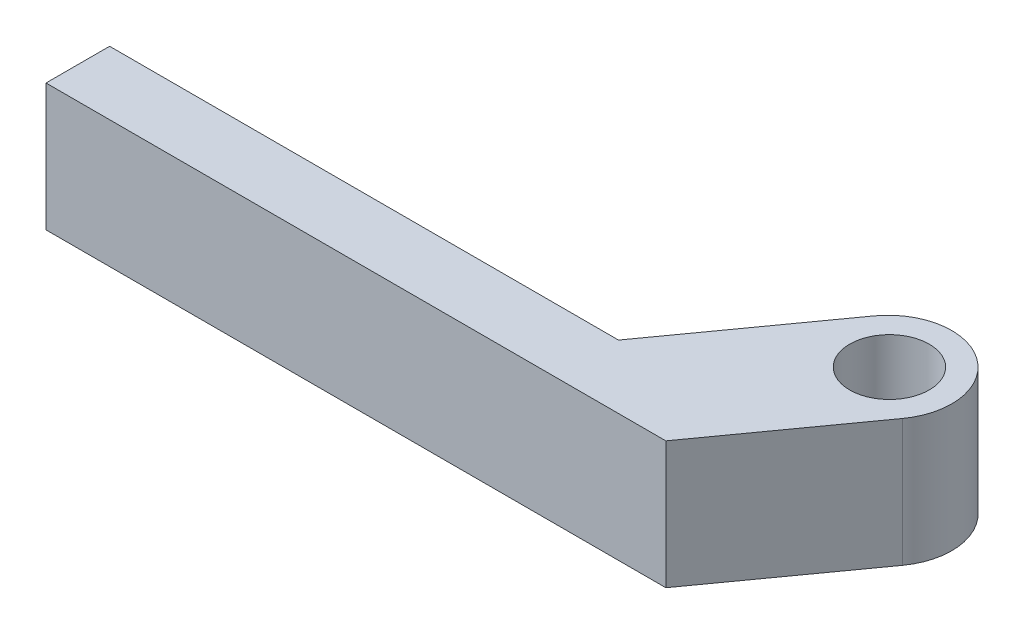
SolidWorks part; units mm, degrees
ref_plane "Front Plane" through (0, 0, 0) normal (0, 0, 1) x (1, 0, 0)
ref_plane "Top Plane" through (0, 0, 0) normal (0, 1, 0) x (1, 0, 0)
ref_plane "Right Plane" through (0, 0, 0) normal (1, 0, 0) x (0, 0, -1)
sketch "Sketch2" plane through (0, 0, 0) normal (0, 1, 0) x (1, 0, 0)
  line L5 (-10.6389, -35.243) -> (0.0062, -20.4255)
  line L7 (-61.4389, -41.593) -> (-10.6389, -41.593)
  line L8 (-61.4389, -41.593) -> (-61.4389, -35.243)
  line L9 (-61.4389, -35.243) -> (-10.6389, -35.243)
  line L10 (-10.6389, -41.593) -> (-10.6389, -35.243) construction
  line L11 (-61.4389, -41.593) -> (-10.6389, -35.243) construction
  line L12 (-61.4389, -35.243) -> (-10.6389, -41.593) construction
  line L14 (-10.6389, -41.593) -> (0.4368, -41.593)
  line L18 (10.3205, -27.8354) -> (0.4368, -41.593)
  line L19 (0.0062, -20.4255) -> (10.3205, -27.8354) construction
  line L20 (5.1633, -17.7805) -> (-45.4817, -17.7805) construction
  arc A2 (0.0062, -20.4255) -> (10.3205, -27.8354) centre (5.1633, -24.1305) cw
  point P5 (-36.0389, -38.418)
  dimension "D2" = 12.7
  dimension "D3" = 17.4625
  dimension "D4" = 6.35
  dimension "D10" = 50.8
extrude "Boss-Extrude1" add sketch "Sketch2" along normal blind 12.7
hole_wizard "3/8-16 Tapped Hole1" positions "Sketch3" profile "Sketch4" tap size "3/8-16" standard "ANSI Inch"
sketch "Sketch3" plane through (0, 12.7, 0) normal (0, 1, 0) x (1, 0, 0)
  line L0 (0.4368, -41.593) -> (10.3205, -27.8354) construction
  arc A0 (10.3205, -27.8354) -> (0.0062, -20.4255) centre (5.1633, -24.1305) ccw construction
  point P0 (5.2187, -24.0534)
  point P6 (8.8683, -18.9734)
  dimension "D1" = 5.08
  dimension "D2" = 6.35
sketch "Sketch4" plane through (5.2187, 12.7, 24.0534) normal (1, 0, 0) x (0, 0, 1)
  line L0 (0, 0) -> (0, 8.7347)
  line L1 (0, 8.7347) -> (3.9687, 6.35)
  line L2 (3.9687, 6.35) -> (3.9688, 0)
  line L5 (3.9688, 0) -> (0, 0)
  line L10 (0, 8.7347) -> (-3.9688, 6.35) construction
  line L11 (0, -6.35) -> (0, 107.95) construction
  dimension "Tap Drill Dia." = 7.9375
  dimension "Tap Drill Depth" = 6.35
  dimension "Drill Angle" = 118
cosmetic thread "Hole Thread1"
sketch "Sketch5" plane through (0, 12.7, 0) normal (0, 1, 0) x (1, 0, 0)
  line L0 (5.1633, -17.7805) -> (-38.0048, -17.7805) construction
  arc A0 (10.3205, -27.8354) -> (0.0062, -20.4255) centre (5.1633, -24.1305) ccw construction
